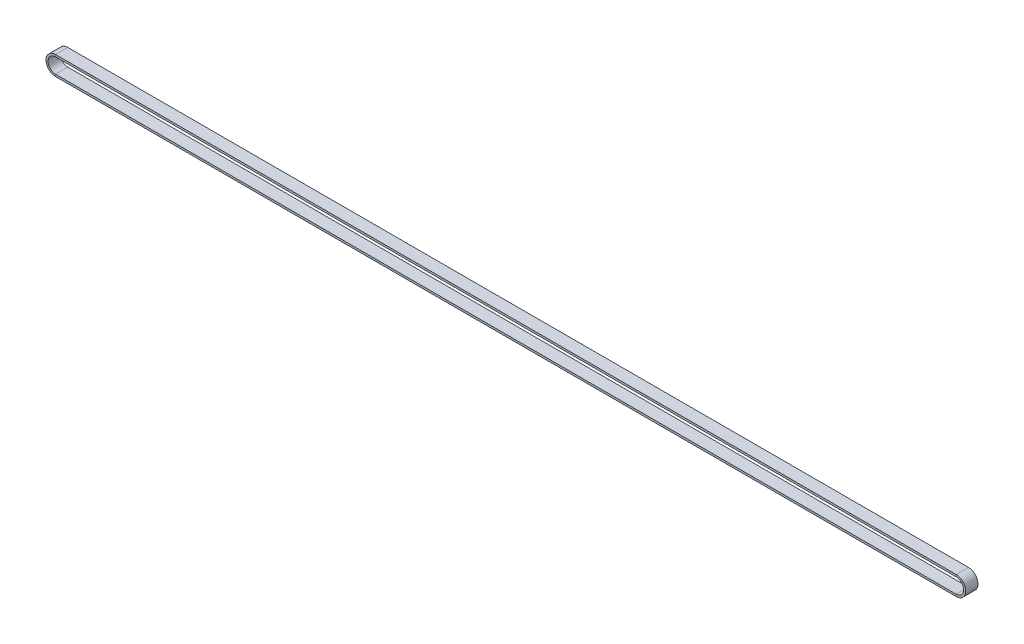
SolidWorks part; units mm, degrees
ref_plane "Front Plane" through (0, 0, 0) normal (0, 0, 1) x (1, 0, 0)
ref_plane "Top Plane" through (0, 0, 0) normal (0, 1, 0) x (1, 0, 0)
ref_plane "Right Plane" through (0, 0, 0) normal (1, 0, 0) x (0, 0, -1)
sketch "Sketch2" plane through (0, 0, 0) normal (0, 0, 1) x (1, 0, 0)
  line L0 (0, 0) -> (1, 0) construction
  line L1 (0, 0) -> (0, 1) construction
  line L2 (0, -7) -> (-660.3327, -7)
  line L3 (-660.3327, 7) -> (0, 7)
  arc A0 (0, 7) -> (0, -7) centre (0, 0) cw
  arc A1 (-660.3327, -7) -> (-660.3327, 7) centre (-660.3327, 0) cw
sketch "Sketch3" plane through (0, 0, 0) normal (1, 0, 0) x (0, 0, -1)
  line L0 (0, 7) -> (0, -7) construction
  line L1 (0, 7) -> (-9, 7)
  line L2 (0, 7) -> (0, 5.5)
  line L3 (0, 5.5) -> (-9, 5.5)
  line L4 (-9, 7) -> (-9, 5.5)
  dimension "D1" = 1.5
  dimension "D2" = 9
sweep "Sweep1" add profiles "Sketch3" path "Sketch2"
